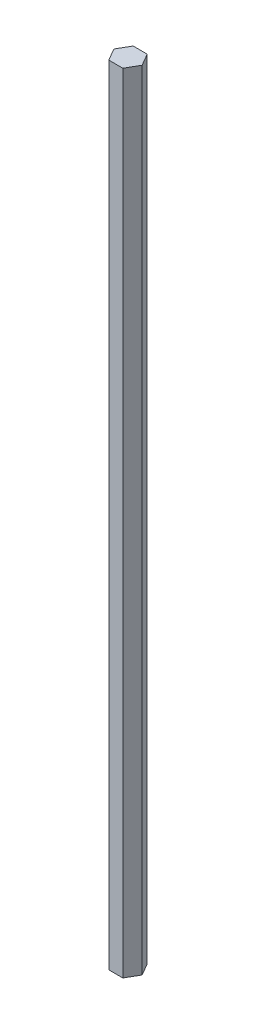
SolidWorks part; units mm, degrees
ref_plane "Front Plane" through (0, 0, 0) normal (0, 0, 1) x (1, 0, 0)
ref_plane "Top Plane" through (0, 0, 0) normal (0, 1, 0) x (1, 0, 0)
ref_plane "Right Plane" through (0, 0, 0) normal (1, 0, 0) x (0, 0, -1)
sketch "Sketch1" plane through (0, 0, 0) normal (0, 1, 0) x (1, 0, 0)
  line L1 (3.6662, -6.35) -> (7.3323, 0)
  line L2 (7.3323, 0) -> (3.6662, 6.35)
  line L3 (3.6662, 6.35) -> (-3.6662, 6.35)
  line L4 (-3.6662, 6.35) -> (-7.3323, 0)
  line L5 (-7.3323, 0) -> (-3.6662, -6.35)
  line L6 (-3.6662, -6.35) -> (3.6662, -6.35)
  circle A0 centre (0, 0) radius 6.35 construction
  dimension "D1" = 12.7
extrude "Boss-Extrude1" add sketch "Sketch1" along normal blind 410.464
sketch "Sketch2" plane through (0, 0, 0) normal (0, -1, 0) x (1, 0, 0)
  point P0 (0, 0)
sketch "Sketch3" plane through (0, 410.464, 0) normal (0, 1, 0) x (1, 0, 0)
  point P0 (0, 0)
ref_axis "Axis1" through (0, 468.6451, 0) along (0, -1, 0)
